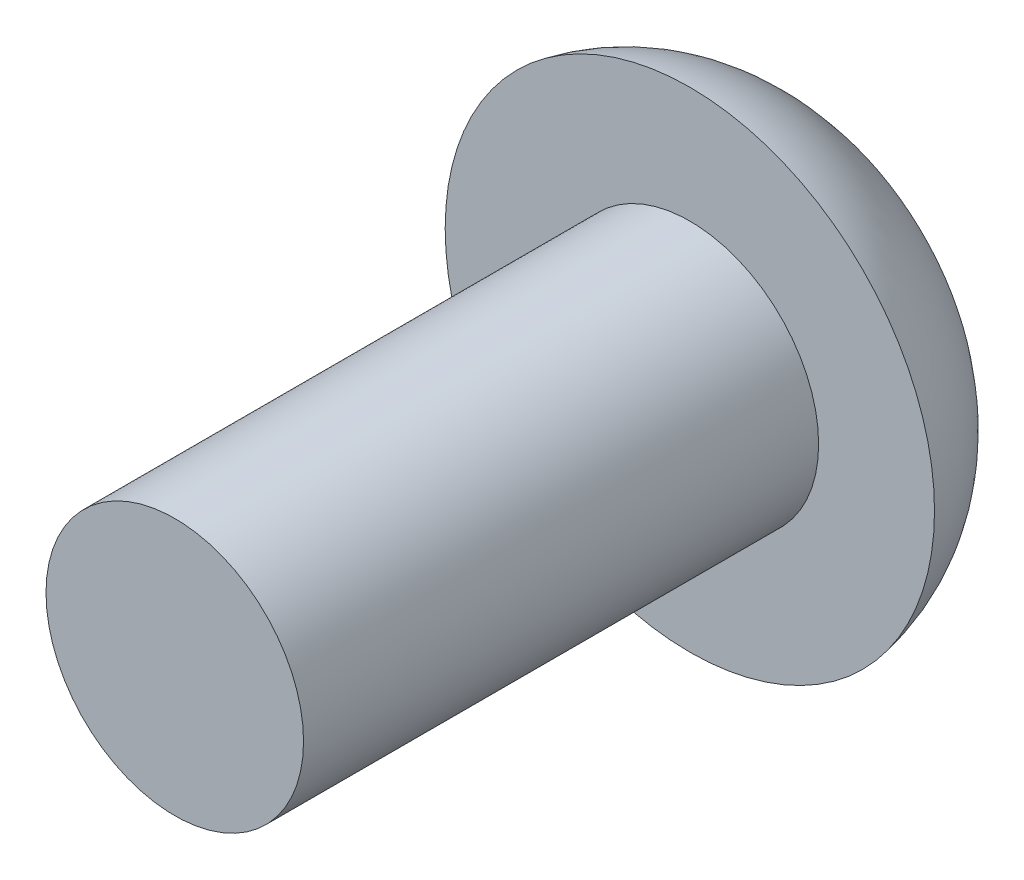
SolidWorks part; units mm, degrees
ref_plane "前视基准面" through (0, 0, 0) normal (0, 0, 1) x (1, 0, 0)
ref_plane "上视基准面" through (0, 0, 0) normal (0, 1, 0) x (1, 0, 0)
ref_plane "右视基准面" through (0, 0, 0) normal (1, 0, 0) x (0, 0, -1)
sketch "草图1" plane through (0, 0, 0) normal (0, 0, 1) x (1, 0, 0)
  circle A0 centre (0, 0) radius 1.5
extrude "凸台-拉伸1" add sketch "草图1" along normal blind 6
sketch "草图2" plane through (0, 0, 0) normal (0, 0, -1) x (-1, 0, 0)
  circle A0 centre (0, 0) radius 2.85
extrude "凸台-拉伸2" add sketch "草图2" along normal blind 1.65
fillet "圆角1" radius 2 1 edges at (-2.85, 0, -1.65)
sketch "草图3" plane through (0, 0, 0) normal (0, 0, 1) x (1, 0, 0)
  circle A0 centre (0, 0) radius 1.55
  dimension "D1" = 3.1
